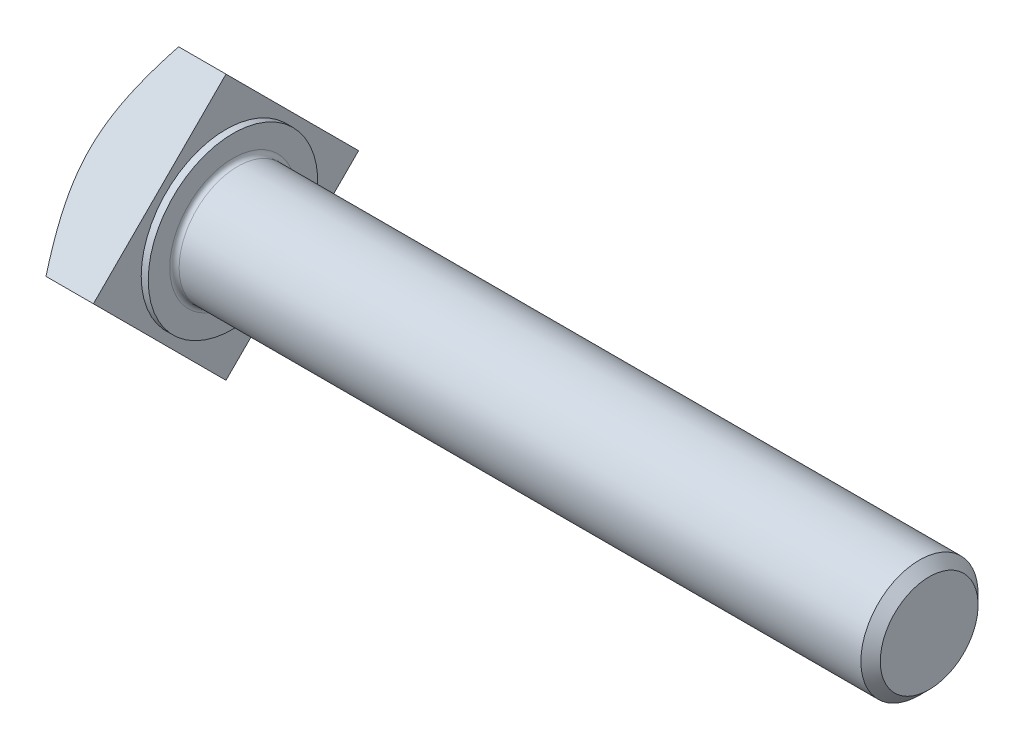
SolidWorks part; units mm, degrees
ref_plane "Front Plane" through (0, 0, 0) normal (0, 0, 1) x (1, 0, 0)
ref_plane "Top Plane" through (0, 0, 0) normal (0, 1, 0) x (1, 0, 0)
ref_plane "Right Plane" through (0, 0, 0) normal (1, 0, 0) x (0, 0, -1)
sketch "BaseHeadSke" plane through (0, 0, 0) normal (1, 0, 0) x (0, 0, -1)
  line L0 (-33.7114, 0) -> (29.9357, 0) construction
  line L1 (0, 35.0598) -> (0, -29.1266) construction
  line L2 (0, 11.3137) -> (11.3137, 0)
  line L3 (11.3137, 0) -> (0, -11.3137)
  line L4 (0, -11.3137) -> (-11.3137, 0)
  line L5 (-11.3137, 0) -> (0, 11.3137)
  dimension "Head_sidewidth" = 16
extrude "BaseHead" add sketch "BaseHeadSke" along normal blind 6.4
sketch "BodySke" plane through (0, 0, 0) normal (0, 0, 1) x (1, 0, 0)
  line L0 (0, 0) -> (81.8774, 0) construction
  line L1 (6.4, 0) -> (6.4, 7.235)
  line L2 (6.4, 11.3137) -> (6.4, 0) construction
  line L3 (6.4, 7.235) -> (7, 7.235)
  line L4 (7, 7.235) -> (7, 5)
  line L5 (7, 5) -> (65.572, 5)
  line L6 (65.572, 5) -> (66.4, 4.172)
  line L7 (66.4, 4.172) -> (66.4, 0)
  line L8 (66.4, 0) -> (6.4, 0)
  line L9 (7.9, 0) -> (7.9, 9.1784) construction
  line L10 (40.4, 0) -> (40.4, 9.1784) construction
  dimension "Thread_length" = 26
  dimension "Advance" = 1.5
  dimension "Thread_minor" = 8.344
revolve "BaseBody" add sketch "BodySke" angle 360 about L0
cosmetic thread "ThreadCosmetic" [suppressed] parameters "Thread_length"=26, "Thread_minor"=8.344
fillet "Fillet1" radius 0.4 1 edges at (7, 0, 5)
sketch "HeadChamferSke" plane through (0, 0, 0) normal (0, 0, 1) x (1, 0, 0)
  line L0 (0, 0) -> (67.5964, 0) construction
  line L1 (0, 11.3137) -> (0, 7.235)
  line L2 (0, 7.235) -> (2.3548, 11.3137)
  line L3 (2.3548, 11.3137) -> (0, 11.3137)
  line L4 (6.4, 11.3137) -> (0, 11.3137) construction
  line L5 (0, 11.3137) -> (0, 0) construction
  dimension "Head_chamfer_angle" = 30
revolve "HeadChamfer" cut sketch "HeadChamferSke" angle 360 about L0
sketch "ThdSchSke" plane through (0, 0, 0) normal (0, 0, 1) x (1, 0, 0)
  line L0 (0, 0) -> (70.3562, 0) construction
  line L1 (0, 0) -> (81.8774, 0) construction
  line L2 (64.072, 5.9561) -> (64.072, 5)
  line L3 (64.072, 5.9561) -> (65.0281, 5.9561)
  line L4 (65.0281, 5.9561) -> (65.0281, 5)
  line L5 (65.0281, 5) -> (64.55, 4.172)
  line L6 (64.55, 4.172) -> (64.072, 5)
  dimension "D1" = 1.5
revolve "ThreadSchematic" [suppressed] cut sketch "ThdSchSke" angle 360 about L0
pattern_linear "ThdSchPat" [suppressed] of bodies 116
equation "\"D1@ThdSchSke\" = \"Advance@BodySke\""
equation "\"Tooth_Num@ThdSchPat\" =  int( \"Thread_length@BodySke\" / \"Advance@BodySke\" ) "
equation "\"Advance@ThdSchPat\" = \"Advance@BodySke\""
equation "\"Thread_minor@ThreadCosmetic\" = \"Thread_minor@BodySke\""
